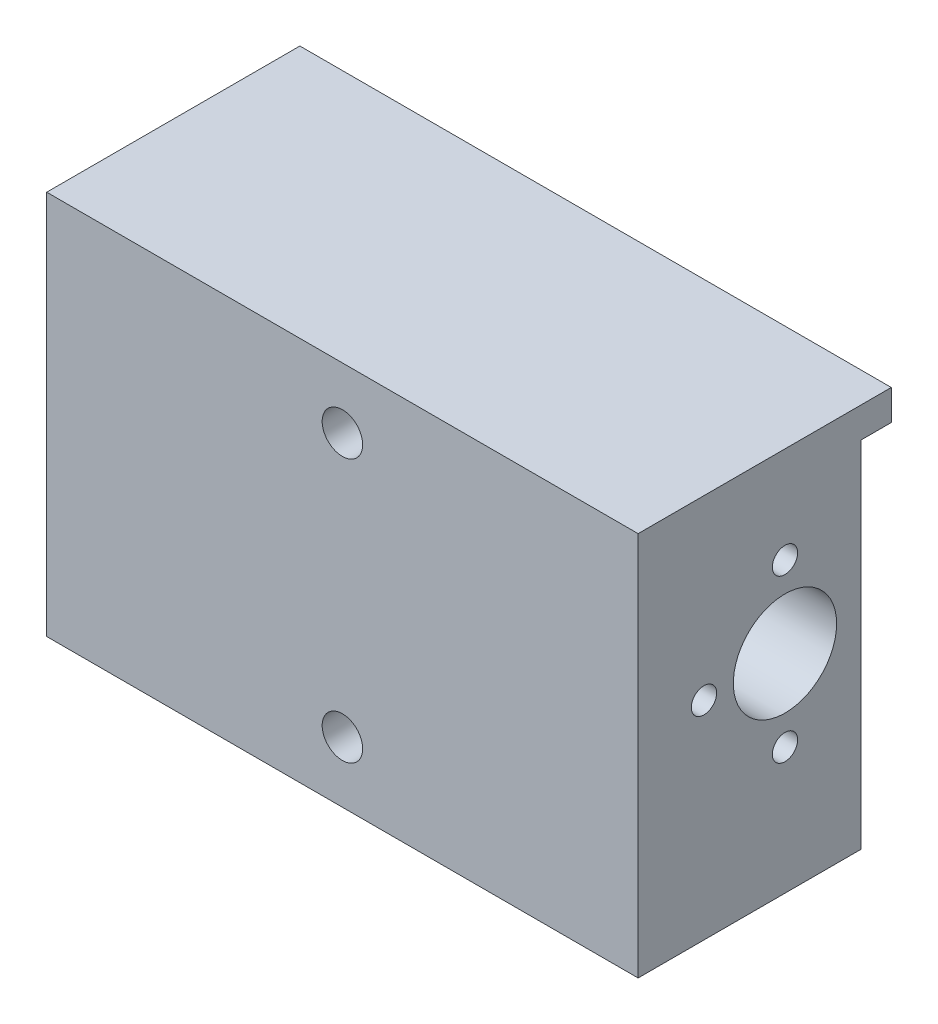
SolidWorks part; units mm, degrees
ref_plane "Alzado" through (0, 0, 0) normal (0, 0, 1) x (1, 0, 0)
ref_plane "Planta" through (0, 0, 0) normal (0, 1, 0) x (1, 0, 0)
ref_plane "Vista lateral" through (0, 0, 0) normal (1, 0, 0) x (0, 0, -1)
sketch "Croquis1" plane through (0, 0, 0) normal (0, 0, 1) x (1, 0, 0)
  line L1 (0, 0) -> (58.4, 0)
  line L2 (0, 0) -> (0, 38)
  line L3 (0, 38) -> (58.4, 38)
  line L4 (58.4, 0) -> (58.4, 38)
  dimension "D1" = 38
  dimension "D2" = 58.4
extrude "Saliente-Extruir1" add sketch "Croquis1" along normal blind 22
sketch "Croquis2" plane through (58.4, 0, 0) normal (1, 0, 0) x (0, 0, -1)
  line L1 (-22, 0) -> (-22, 38) construction
  line L2 (-22, 38) -> (0, 38) construction
  circle A0 centre (-7.5, 20.5) radius 5.1
  dimension "D1" = 10.2
  dimension "D2" = 14.5
  dimension "D3" = 17.5
extrude "Cortar-Extruir1" cut sketch "Croquis2" against normal through all
hole_wizard "Taladros de espiga de Ø4.0mm2" positions "Croquis4" profile "Croquis5" hole size "Ø4.0" standard "DIN"
sketch "Croquis4" plane through (0, 0, 22) normal (0, 0, 1) x (1, 0, 0)
  line L0 (0, 32) -> (58.4, 32) construction
  line L1 (0, 38) -> (0, 0) construction
  line L2 (58.4, 0) -> (58.4, 38) construction
  line L5 (58.4, 6) -> (0, 6) construction
  line L7 (58.4, 38) -> (0, 38) construction
  line L8 (29.2, 38) -> (29.2, 0) construction
  line L9 (0, 0) -> (58.4, 0) construction
  point P24 (29.2, 32)
  point P26 (29.2, 6)
  dimension "D1" = 6
  dimension "D2" = 6
sketch "Croquis5" plane through (29.2, 6, 22) normal (1, 0, 0) x (0, -1, 0)
  line L0 (0, 0) -> (0, 15.2017)
  line L1 (0, 15.2017) -> (2, 14)
  line L2 (2, 14) -> (2, 0)
  line L5 (2, 0) -> (0, 0)
  line L10 (0, 15.2017) -> (-2, 14) construction
  line L11 (0, -6.35) -> (0, 107.95) construction
  dimension "Diámetro de taladro" = 4
  dimension "Profundidad de taladro" = 14
  dimension "Ángulo de perforador" = 118
sketch "Croquis6" plane through (0, 0, 0) normal (0, 0, -1) x (-1, 0, 0)
  line L1 (-58.4, 35) -> (0, 35)
  line L2 (-58.4, 35) -> (-58.4, 38)
  line L3 (-58.4, 38) -> (0, 38)
  line L4 (0, 35) -> (0, 38)
  dimension "D1" = 3
extrude "Saliente-Extruir2" add sketch "Croquis6" along normal blind 3
hole_wizard "Perforador para roscar para macho de roscar para M32" positions "Croquis10" profile "Croquis11" hole size "M3" standard "DIN"
sketch "Croquis10" plane through (58.4, 0, 0) normal (1, 0, 0) x (0, 0, -1)
  line L0 (-7.5, 12.5) -> (-7.5, 28.5) construction
  line L2 (-15.5, 20.5) -> (-7.5, 20.5) construction
  circle A0 centre (-7.5, 20.5) radius 8 construction
  point P5 (-7.5, 12.5)
  point P6 (-7.5, 28.5)
  point P8 (-15.5, 20.5)
  dimension "D1" = 16
sketch "Croquis11" plane through (58.4, 20.5, 15.5) normal (0, 1, 0) x (0, 0, -1)
  line L0 (0, 0) -> (0, 14.7511)
  line L1 (0, 14.7511) -> (1.25, 14)
  line L2 (1.25, 14) -> (1.25, 0)
  line L5 (1.25, 0) -> (0, 0)
  line L10 (0, 14.7511) -> (-1.25, 14) construction
  line L11 (0, -6.35) -> (0, 107.95) construction
  dimension "Diámetro de taladro" = 2.5
  dimension "Profundidad de taladro" = 14
  dimension "Ángulo de perforador" = 118
